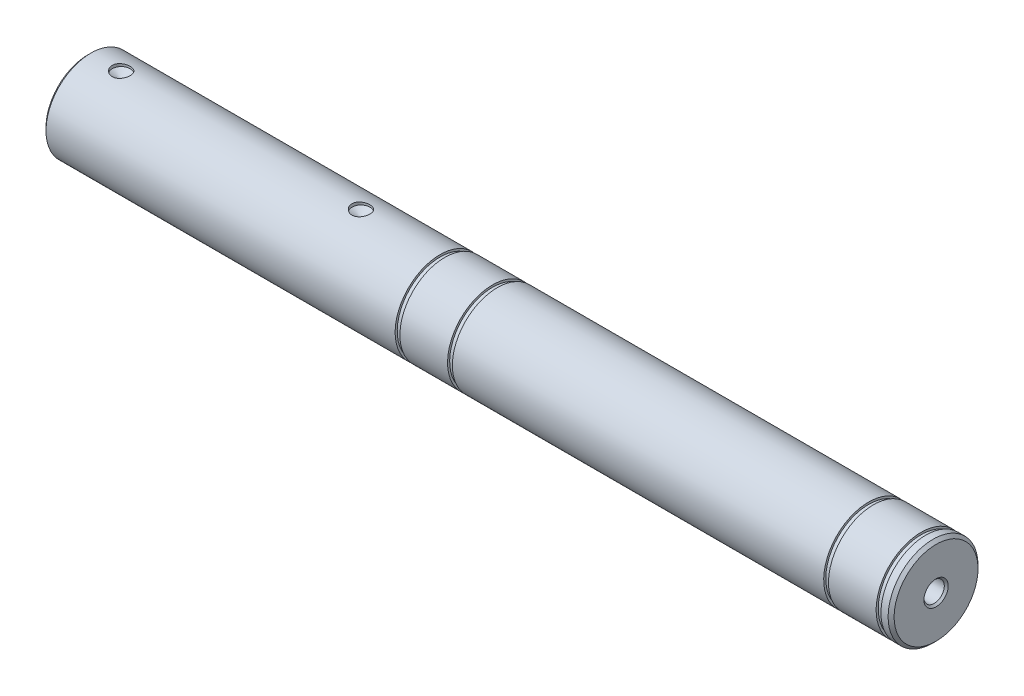
SolidWorks part; units mm, degrees
material "1.4305 (X8CrNiS18-9)"
ref_plane "Ebene1" through (0, 0, 0) normal (0, 0, 1) x (1, 0, 0)
ref_plane "Ebene2" through (0, 0, 0) normal (0, 1, 0) x (1, 0, 0)
ref_plane "Ebene3" through (0, 0, 0) normal (1, 0, 0) x (0, 0, -1)
ref_axis "Achse1" through (-159.7554, 0, 0) along (1, 0, 0)
sketch "Skizze1" plane through (0, 0, 0) normal (0, 0, 1) x (1, 0, 0)
  line L1 (-141.5, 14) -> (-141.5, 0)
  line L2 (119, 15) -> (119, 14.3)
  line L3 (119, 14.3) -> (120.6, 14.3)
  line L4 (120.6, 14.3) -> (120.6, 15)
  line L5 (-24, 15) -> (-24, 14.3)
  line L6 (-140.5, 15) -> (-24, 15)
  line L7 (-24, 14.3) -> (-22.4, 14.3)
  line L8 (-22.4, 14.3) -> (-22.4, 15)
  line L9 (-141.5, 0) -> (141.5, 0)
  line L10 (136.5, 14.3) -> (138.1, 14.3)
  line L11 (-140.5, 15) -> (-141.5, 14)
  line L12 (140.5, 15) -> (141.5, 14)
  line L13 (141.5, 14) -> (141.5, 0)
  line L14 (-241.8552, 0) -> (331.3011, 0) construction
  line L15 (-6.5, 15) -> (-6.5, 14.3)
  line L16 (138.1, 15) -> (140.5, 15)
  line L17 (-6.5, 14.3) -> (-4.9, 14.3)
  line L18 (136.5, 15) -> (136.5, 14.3)
  line L19 (-4.9, 14.3) -> (-4.9, 15)
  line L20 (138.1, 15) -> (138.1, 14.3)
  line L21 (-4.9, 15) -> (119, 15)
  line L22 (-22.4, 15) -> (-6.5, 15)
  line L23 (120.6, 15) -> (136.5, 15)
  point P3 (-141.5, 15)
  point P14 (141.5, 15)
  point P25 (0, 0)
  dimension "D2" = 17.5
  dimension "D3" = 283
  dimension "D4" = 17.5
  dimension "D5" = 117.5
  dimension "D6" = 143
  dimension "D7" = 30
  dimension "D8" = 3.4
  dimension "D10" = 28.6
  dimension "D11" = 1.6
revolve "Basis-Rotation" add sketch "Skizze1" angle 360 about L14
hole_wizard "M8 Gewindebohrung1" positions "Skizze4" profile "Skizze3" tap size "M8" standard "Gabler-Normteile"
sketch "Skizze4" plane through (-141.5, 0, 0) normal (-1, 0, 0) x (0, 0, 1)
  point P0 (0, 0)
sketch "Skizze3" plane through (-141.5, 0, 0) normal (0, 1, 0) x (0, 0, 1)
  line L0 (0, 0) -> (0, 28.2929)
  line L1 (0, 28.2929) -> (3.4, 26.25)
  line L2 (3.4, 26.25) -> (3.4, 0.65)
  line L3 (3.4, 0.65) -> (4.05, 0)
  line L5 (4.05, 0) -> (0, 0)
  line L6 (-3.4, 0.65) -> (-4.05, 0) construction
  line L10 (0, 28.2929) -> (-3.4, 26.25) construction
  line L11 (0, -6.35) -> (0, 107.95) construction
  dimension "Bohrerdurchmesser" = 6.8
  dimension "Bohrungstiefe" = 26.25
  dimension "Senkdurchmesser (Oben)" = 8.1
  dimension "Senkwinkel (Oben)" = 90
  dimension "Spitzenwinkel" = 118
cosmetic thread "Bohrungsgewinde1" parameters "D1"=20, "D2"=8
hole_wizard "M8 Gewindebohrung2" positions "Skizze6" profile "Skizze5" tap size "M8" standard "Gabler-Normteile"
sketch "Skizze6" plane through (141.5, 0, 0) normal (1, 0, 0) x (0, 0, -1)
  point P0 (0, 0)
sketch "Skizze5" plane through (141.5, 0, 0) normal (0, 1, 0) x (0, 0, -1)
  line L0 (0, 0) -> (0, 28.2929)
  line L1 (0, 28.2929) -> (3.4, 26.25)
  line L2 (3.4, 26.25) -> (3.4, 0.65)
  line L3 (3.4, 0.65) -> (4.05, 0)
  line L5 (4.05, 0) -> (0, 0)
  line L6 (-3.4, 0.65) -> (-4.05, 0) construction
  line L10 (0, 28.2929) -> (-3.4, 26.25) construction
  line L11 (0, -6.35) -> (0, 107.95) construction
  dimension "Bohrerdurchmesser" = 6.8
  dimension "Bohrungstiefe" = 26.25
  dimension "Senkdurchmesser (Oben)" = 8.1
  dimension "Senkwinkel (Oben)" = 90
  dimension "Spitzenwinkel" = 118
cosmetic thread "Bohrungsgewinde2" parameters "D1"=20, "D2"=8
ref_plane "Ebene13" through (0, 15, 0) normal (0, 1, 0) x (1, 0, 0)
hole_wizard "Ø6.0 (6) Durchmesser Bohrung1" positions "Skizze34" profile "Skizze33" hole size "Ø6.0" standard "Gabler-Normteile"
sketch "Skizze34" plane through (0, 15, 0) normal (0, 1, 0) x (1, 0, 0)
  line L0 (0, 0) -> (-129.5329, 0) construction
  line L1 (-141.5, 14) -> (-141.5, -14) construction
  point P5 (-130.4, 0)
  point P7 (-50.4, 0)
  dimension "D1" = 11.1
  dimension "D2" = 80
sketch "Skizze33" plane through (-50.4, 15, 0) normal (1, 0, 0) x (0, 0, 1)
  line L0 (0, 0) -> (0, 2.8026)
  line L1 (0, 2.8026) -> (3, 1)
  line L2 (3, 1) -> (3, 0)
  line L5 (3, 0) -> (0, 0)
  line L10 (0, 2.8026) -> (-3, 1) construction
  line L11 (0, -6.35) -> (0, 107.95) construction
  dimension "Bohrerdurchmesser" = 6
  dimension "Bohrungstiefe" = 1
  dimension "Spitzenwinkel" = 118
